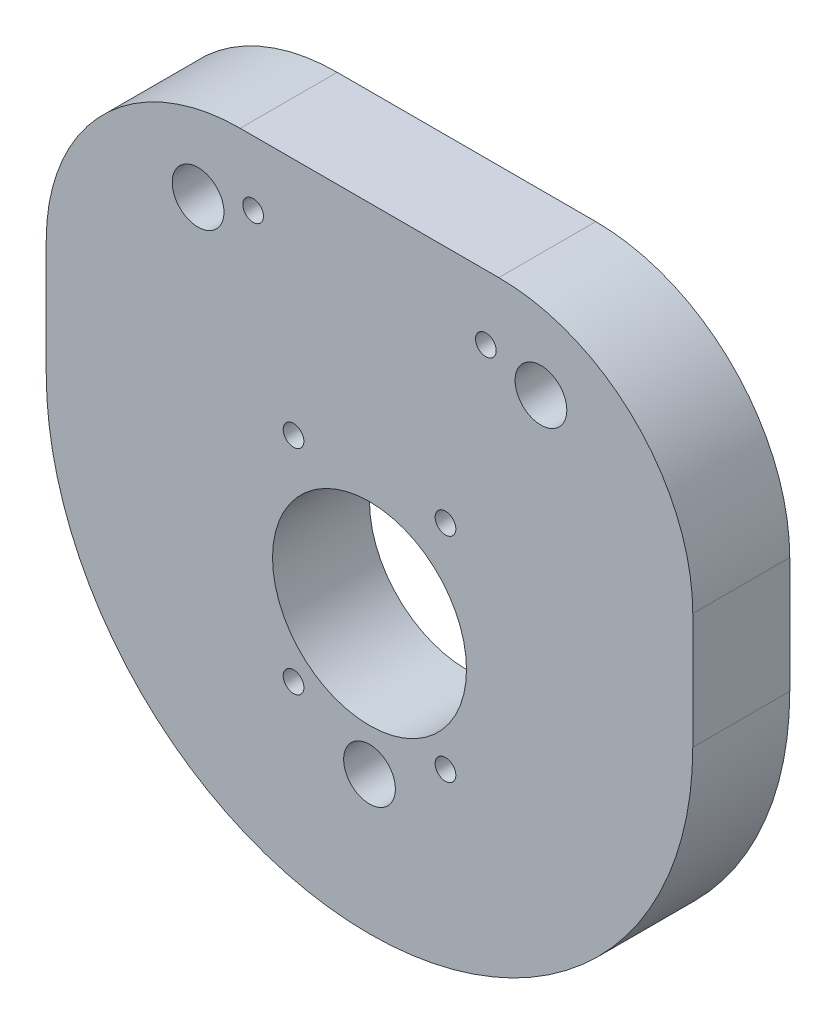
SolidWorks part; units mm, degrees
ref_plane "Front Plane" through (0, 0, 0) normal (0, 0, 1) x (1, 0, 0)
ref_plane "Top Plane" through (0, 0, 0) normal (0, 1, 0) x (1, 0, 0)
ref_plane "Right Plane" through (0, 0, 0) normal (1, 0, 0) x (0, 0, -1)
sketch "Sketch1" plane through (0, 0, 0) normal (0, 0, 1) x (1, 0, 0)
  line L0 (4, 20) -> (-4, 20) construction
  line L1 (-50, 20) -> (50, 20)
  line L2 (-50, 20) -> (-50, -77.9165)
  line L3 (-50, -77.9165) -> (50, -77.9165)
  line L4 (50, 20) -> (50, -77.9165)
  circle A0 centre (18, 10) radius 1.6
  circle A1 centre (-18, 10) radius 1.6
  circle A2 centre (-11.75, -17) radius 1.6
  circle A3 centre (11.75, -17) radius 1.6
  circle A4 centre (11.75, -50) radius 1.6
  circle A5 centre (-11.75, -50) radius 1.6
  point P6 (0, -77.9165)
  dimension "D2" = 3.2
  dimension "D1" = 100
extrude "Boss-Extrude1" add sketch "Sketch1" along normal blind 15
sketch "Sketch2" plane through (0, 0, 15) normal (0, 0, 1) x (1, 0, 0)
  circle A0 centre (-26.5165, 7.5) radius 4
  circle A1 centre (26.5165, 7.5) radius 4
  circle A2 centre (0, -56.5165) radius 4
  dimension "D1" = 8
extrude "Cut-Extrude1" cut sketch "Sketch2" against normal offset from surface (12 mm away) 3 up to face at (0, -28.9582, 0)
fillet "Fillet1" radius 50 2 edges at (-50, -77.9165, 7.5) (50, -77.9165, 7.5)
fillet "Fillet2" radius 30 2 edges at (-50, 20, 7.5) (50, 20, 7.5)
sketch "Sketch3" plane through (0, 0, 0) normal (0, 0, -1) x (-1, 0, 0)
  circle A0 centre (0, -35) radius 15
  point P2 (0, 0)
  dimension "D2" = 30
  dimension "D1" = 35
extrude "Cut-Extrude2" cut sketch "Sketch3" against normal through all both and the other way through all
